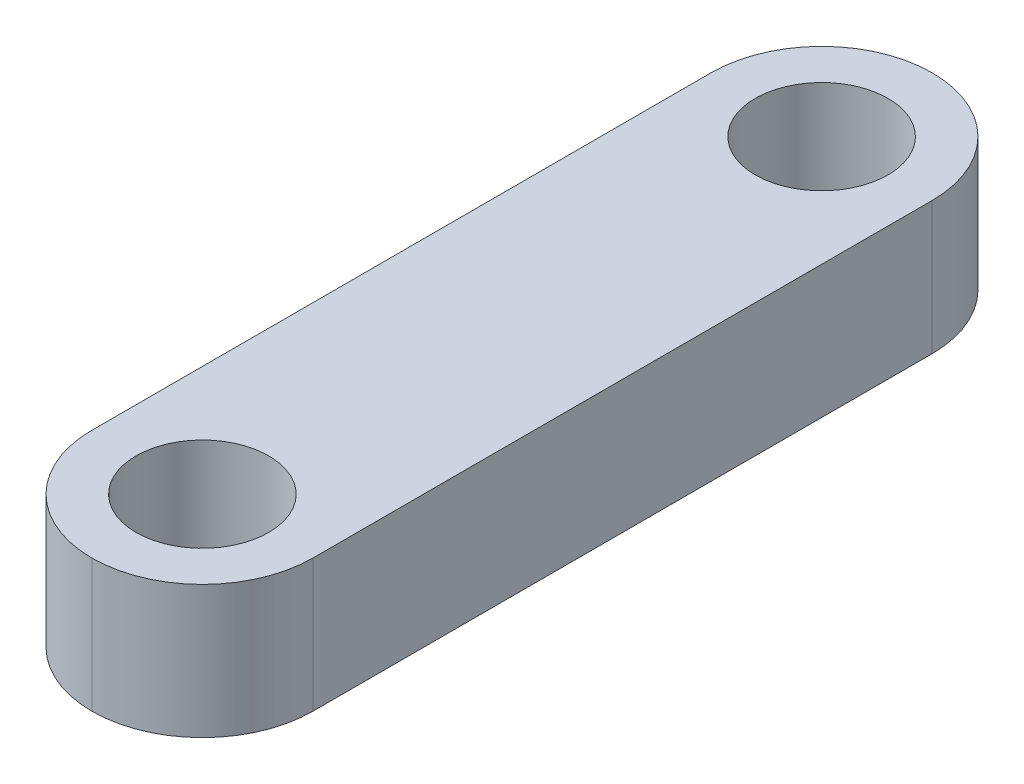
SolidWorks part; units mm, degrees
ref_plane "前视基准面" through (0, 0, 0) normal (0, 0, 1) x (1, 0, 0)
ref_plane "上视基准面" through (0, 0, 0) normal (0, 1, 0) x (1, 0, 0)
ref_plane "右视基准面" through (0, 0, 0) normal (1, 0, 0) x (0, 0, -1)
other "Configuration Table"
sketch "Sketch1" plane through (0, 0, 0) normal (0, 1, 0) x (1, 0, 0)
  line L0 (0.4697, 11.1503) -> (0.4697, -7.8497) construction
  line L1 (-2.0303, 11.1503) -> (2.9697, 11.1503)
  line L2 (-2.0303, 11.1503) -> (-2.0303, -7.8497)
  line L3 (-2.0303, -7.8497) -> (2.9697, -7.8497)
  line L4 (2.9697, 11.1503) -> (2.9697, -7.8497)
  circle A0 centre (0.4697, -5.3497) radius 1.5
  circle A1 centre (0.4697, 8.6503) radius 1.5
  dimension "D3" = 3
  dimension "D4" = 3
  dimension "D1" = 19
  dimension "D2" = 5
  dimension "D5" = 2.5
  dimension "D6" = 2.5
extrude "Boss-Extrude1" add sketch "Sketch1" along normal blind 3
fillet "Fillet1" radius 2.5 4 edges at (2.9697, 1.5, -11.1503) (-2.0303, 1.5, -11.1503) (2.9697, 1.5, 7.8497) (-2.0303, 1.5, 7.8497)
